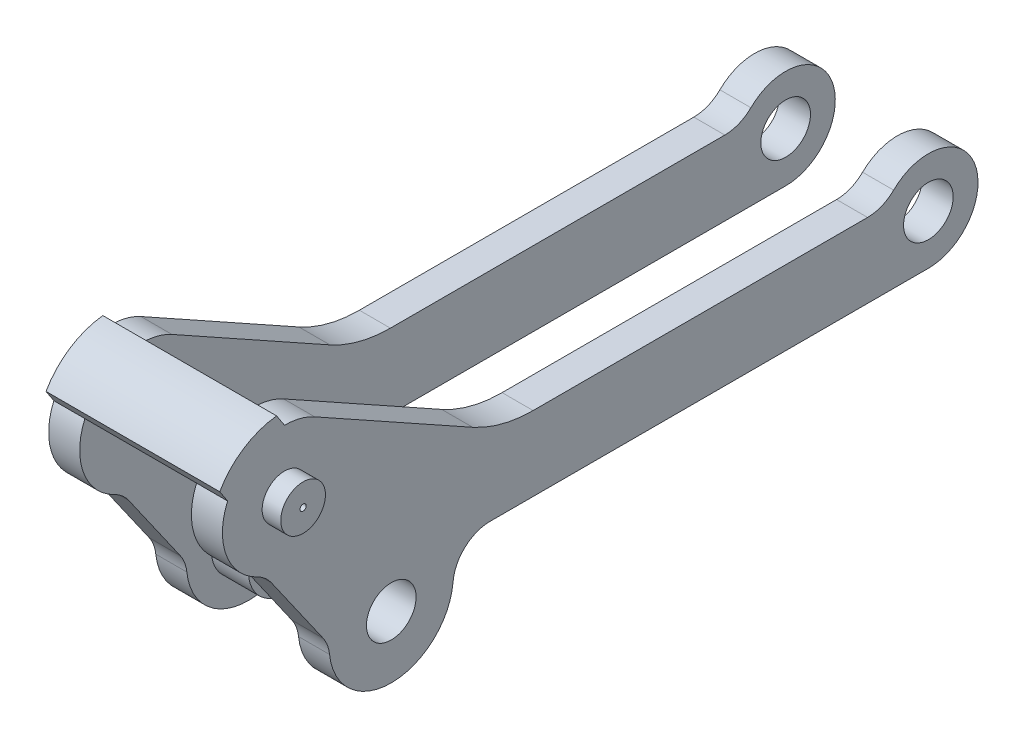
SolidWorks part; units mm, degrees
ref_plane "前视基准面" through (0, 0, 0) normal (0, 0, 1) x (1, 0, 0)
ref_plane "上视基准面" through (0, 0, 0) normal (0, 1, 0) x (1, 0, 0)
ref_plane "右视基准面" through (0, 0, 0) normal (1, 0, 0) x (0, 0, -1)
other "Configuration Table"
sketch "草图1" plane through (0, 0, 0) normal (1, 0, 0) x (0, 0, -1)
  line L1 (0, 0) -> (44.2012, 0)
  line L2 (0, 0) -> (4.2012, -6)
  line L3 (4.2012, -6) -> (44.2012, -6)
  line L4 (44.2012, 0) -> (44.2012, -6)
  line L5 (-10.9556, 1.6987) -> (-4.4024, 6.2873)
  line L6 (-10.9556, 1.6987) -> (-2.352, -10.5886)
  line L7 (-2.352, -10.5886) -> (4.2012, -6)
  line L8 (-4.4024, 6.2873) -> (4.2012, -6)
  circle A0 centre (-7.679, 3.993) radius 5
  circle A1 centre (0.9246, -8.2943) radius 5
  circle A3 centre (44.2012, -2) radius 4
  circle A4 centre (-7.679, 3.993) radius 2
  circle A5 centre (44.2012, -2) radius 2
  circle A6 centre (0.9246, -8.2943) radius 2
  circle A7 centre (0.9246, -8.2943) radius 3
  dimension "D5" = 10
  dimension "D6" = 10
  dimension "D8" = 8
  dimension "D9" = 4
  dimension "D10" = 6
  dimension "D1" = 125
  dimension "D2" = 40
  dimension "D3" = 6
  dimension "D4" = 8
  dimension "D7" = 15
extrude "凸台-拉伸1" add sketch "草图1" along normal blind 2.5 contours A3 L1 L2 A1 L3 | A0 | L8 L5 L6 L7 | A1 | A3 region at (0, -2.9524, -21.636)
extrude "凸台-拉伸2" add sketch "草图1<4>" against normal blind 3 contours A7
sketch "草图1<4>" plane through (0, 0, 0) normal (1, 0, 0) x (0, 0, -1) same geometry as "草图1"
extrude "切除-拉伸1" cut sketch "草图1<3>" along normal through all both and the other way through all contours A4 | A6 | A5
sketch "草图1<3>" plane through (0, 0, 0) normal (1, 0, 0) x (0, 0, -1) same geometry as "草图1"
fillet "圆角1" radius 3 5 edges at (1.25, 0, -40.7371) (1.25, -8.1312, 4.0727) (1.25, -0.7588, 9.2349) (1.25, -6, -5.3672) (1.25, 0, 0)
sketch "草图2" plane through (2.5, 0, 0) normal (1, 0, 0) x (0, 0, -1)
  circle A0 centre (-7.679, 3.993) radius 2
  circle A1 centre (-7.679, 3.993) radius 1.8
  circle A2 centre (-7.679, 3.993) radius 2 construction
  dimension "D1" = 3.6
extrude "凸台-拉伸3" add sketch "草图2" against normal up to surface (2.5 mm away) contours A0 up to face at (0, 3.993, 5.679)
extrude "凸台-拉伸4" add sketch "草图2<3>" along normal blind 1.5 contours A1 region at (2.5, 3.993, 7.679)
sketch "草图2<3>" plane through (2.5, 0, 0) normal (1, 0, 0) x (0, 0, -1) same geometry as "草图2"
ref_plane "基准面1" through (-4.5, 0, 0) normal (-1, 0, 0) x (0, 0, 1)
sketch "草图4" plane through (2.5, 0, 0) normal (1, 0, 0) x (0, 0, -1)
  line L0 (-5.2448, 8.3604) -> (9.7552, 0)
  line L1 (1.5617, 0) -> (39.3023, 0) construction
  line L5 (-5.2448, 0) -> (-5.2448, 8.3604)
  line L6 (-5.2448, 0) -> (9.7552, 0)
  arc A2 (-2.6817, 3.8298) -> (-9.8744, -0.4993) centre (-7.679, 3.993) ccw construction
  dimension "D1" = 15
extrude "凸台-拉伸6" add sketch "草图4" against normal up to surface (2.5 mm away) up to face at (0, -2, -46.2012)
sketch "草图3" plane through (2.5, 0, 0) normal (1, 0, 0) x (0, 0, -1)
  line L0 (-7.679, 3.993) -> (-16.6015, 16.7356) construction
  line L1 (-8.7342, -1.4739) -> (-4.5734, -7.416) construction
  line L2 (-19.3045, 5.993) -> (3.1525, 5.993) construction
  line L7 (-7.679, 8.993) -> (-12.2616, 5.993) construction
  line L8 (-12.2616, 5.993) -> (-13.2566, 7.5129)
  line L9 (9.7552, 0) -> (39.3023, 0) construction
  line L10 (-13.2566, 7.5129) -> (-8.6741, 10.5129) construction
  line L11 (-8.6741, 10.5129) -> (-7.679, 8.993)
  circle A0 centre (-7.679, 3.993) radius 5
  arc A1 (-5.2448, 8.3604) -> (-9.8744, -0.4993) centre (-7.679, 3.993) ccw construction
  circle A2 centre (-7.679, 3.993) radius 2
  circle A3 centre (0.9246, -8.2943) radius 2 construction
  circle A4 centre (-7.679, 3.993) radius 6
  point P7 (-14.0836, 13.1397)
  arc M18 (-5.2448, 8.3604) -> (-9.8744, -0.4993) centre (-7.679, 3.993) ccw
  dimension "D1" = 12
extrude "凸台-拉伸5" add sketch "草图3" against normal up to surface (7 mm away) contours L11 A4 L8 M18 region at (2.5, 8.3868, 10.5555) up to plane "基准面1"
fillet "圆角3" radius 10 1 edges at (1.25, 0, -9.7552)
mirror "镜向1" about plane through (-4.5, 0, 0) normal (-1, 0, 0) of bodies 111
sketch "草图5" plane through (4, 0, 0) normal (1, 0, 0) x (0, 0, -1)
  circle A0 centre (-7.679, 3.993) radius 0.25
  dimension "D1" = 0.5
extrude "切除-拉伸2" cut sketch "草图5" against normal blind 2
